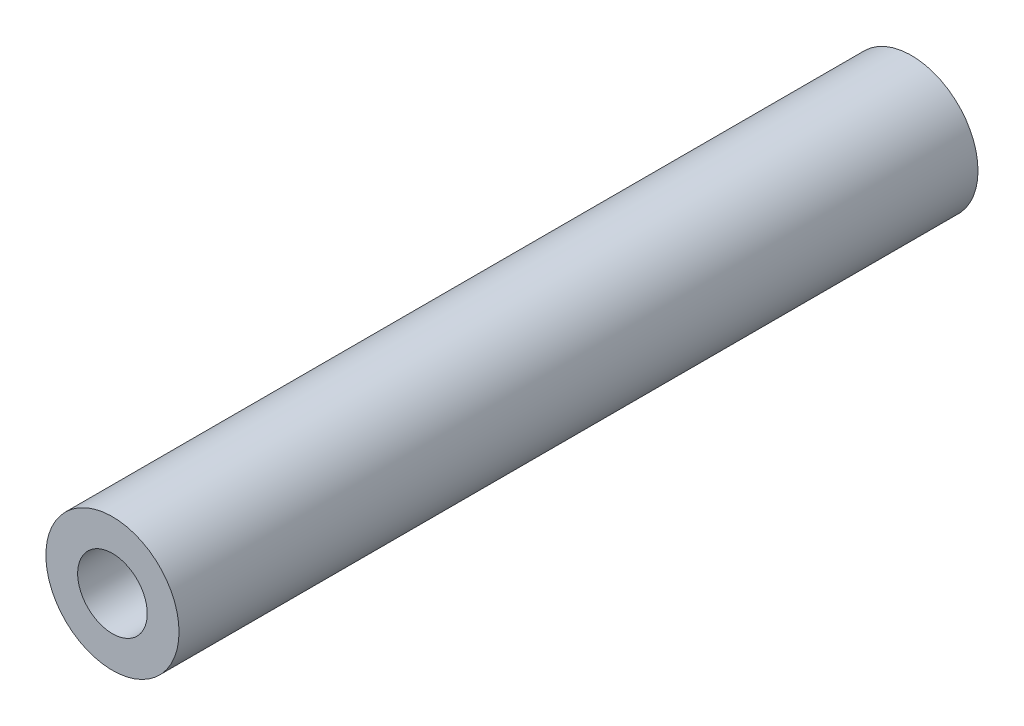
SolidWorks part; units mm, degrees
material "6061-T6 (SS)"
ref_plane "Front Plane" through (0, 0, 0) normal (0, 0, 1) x (1, 0, 0)
ref_plane "Top Plane" through (0, 0, 0) normal (0, 1, 0) x (1, 0, 0)
ref_plane "Right Plane" through (0, 0, 0) normal (1, 0, 0) x (0, 0, -1)
sketch "Sketch1" plane through (0, 0, 0) normal (0, 0, 1) x (1, 0, 0)
  circle A0 centre (0, 0) radius 2.4892
  circle A1 centre (0, 0) radius 4.7625
  dimension "D1" = 4.9784
  dimension "D2" = 9.525
extrude "Boss-Extrude1" add sketch "Sketch1" along normal blind 57.15
